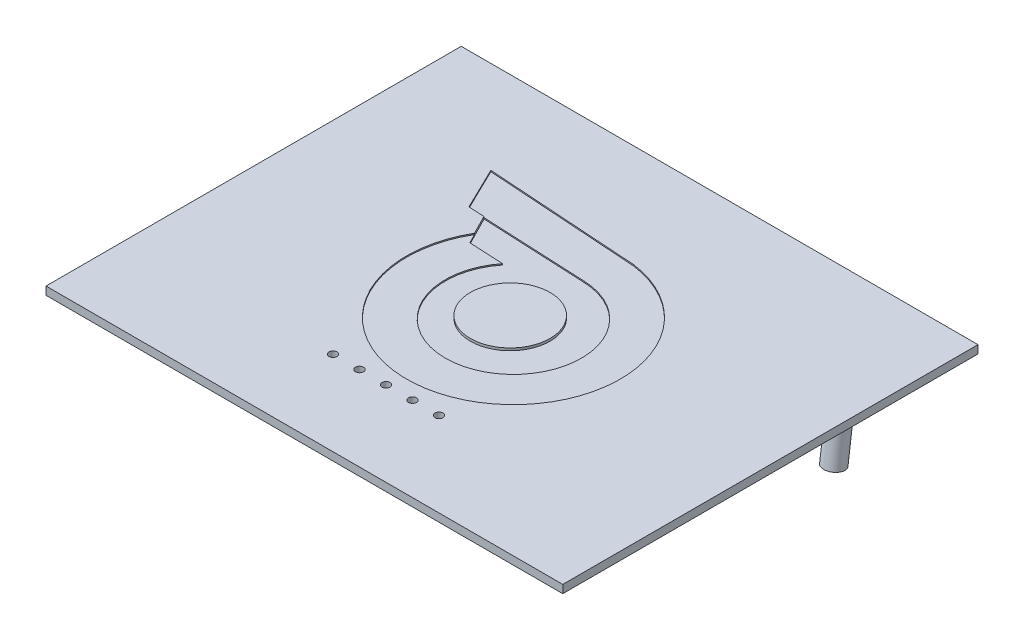
SolidWorks part; units mm, degrees
ref_plane "Front Plane" through (0, 0, 0) normal (0, 0, 1) x (1, 0, 0)
ref_plane "Top Plane" through (0, 0, 0) normal (0, 1, 0) x (1, 0, 0)
ref_plane "Right Plane" through (0, 0, 0) normal (1, 0, 0) x (0, 0, -1)
sketch "Sketch1" plane through (0, 0, 0) normal (0, 1, 0) x (1, 0, 0)
  line L1 (-64, -50.5) -> (64, -50.5)
  line L2 (-64, -50.5) -> (-64, 50.5)
  line L3 (-64, 50.5) -> (64, 50.5)
  line L4 (64, -50.5) -> (64, 50.5)
  line L5 (-64, -50.5) -> (64, 50.5) construction
  line L6 (-64, 50.5) -> (64, -50.5) construction
  point P0 (0, 0)
  dimension "D1" = 101
  dimension "D2" = 128
extrude "Boss-Extrude1" add sketch "Sketch1" along normal blind 2
sketch "Sketch2" plane through (0, 0, 0) normal (0, -1, 0) x (1, 0, 0)
  line L0 (-64, 49) -> (-62.9, 49) construction
  line L1 (-64, 50.5) -> (64, 50.5) construction
  line L2 (64, 49) -> (62.9, 49) construction
  line L3 (64, -50.5) -> (-64, -50.5) construction
  line L4 (62.9, 49) -> (61.7, 49)
  line L5 (62.9, 49) -> (62.9, -49)
  line L6 (62.9, -49) -> (61.7, -49)
  line L7 (61.7, 49) -> (61.7, -49)
  line L8 (-64, -51.87) -> (-64, 50.98) construction
  line L9 (-62.9, 49) -> (-61.7, 49)
  line L10 (-62.9, 49) -> (-62.9, -49)
  line L11 (-62.9, -49) -> (-61.7, -49)
  line L12 (-61.7, 49) -> (-61.7, -49)
  line L13 (-62.9, 49) -> (-62.9, 50.5) construction
  line L14 (64, 50.98) -> (64, -51.87) construction
  dimension "D1" = 1.1
  dimension "D2" = 1.1
  dimension "D3" = 1.2
  dimension "D4" = 1.2
  dimension "D5" = 1.5
  dimension "D6" = 1.5
  dimension "D7" = 1.5
  dimension "D8" = 1.5
extrude "Boss-Extrude2" add sketch "Sketch2" along normal blind 1
sketch "Sketch3" plane through (0, 0, 50.5) normal (0, 0, 1) x (1, 0, 0)
  line L1 (-64, 2) -> (64, 2)
  line L2 (-64, 2) -> (-64, 0)
  line L3 (-64, 0) -> (64, 0)
  line L4 (64, 2) -> (64, 0)
extrude "Boss-Extrude3" add sketch "Sketch3" along normal blind 0.48
sketch "Sketch4" plane through (0, 0, -50.5) normal (0, 0, -1) x (-1, 0, 0)
  line L1 (-64, 2) -> (64, 2)
  line L2 (-64, 2) -> (-64, 0)
  line L3 (-64, 0) -> (64, 0)
  line L4 (64, 2) -> (64, 0)
extrude "Boss-Extrude4" add sketch "Sketch4" along normal blind 1.37
sketch "Sketch5" plane through (0, -10.49, 1.3637) normal (0, 0.9917, -0.1289) x (1, 0, 0)
  circle A1 centre (-58.4589, 22.8979) radius 2.5 construction
  circle A3 centre (-58.4589, 22.8979) radius 2.5
  circle A5 centre (58.5411, 22.8979) radius 2.5 construction
  circle A7 centre (58.5411, 22.8979) radius 2.5
extrude "Boss-Extrude5" add sketch "Sketch5" along normal blind 13 from offset 2
hole_wizard "M3 Clearance Hole1" positions "Sketch7" profile "Sketch6" hole size "M3" standard "ANSI Metric"
sketch "Sketch7" plane through (0, -8.5067, 1.1059) normal (0, -0.9917, 0.1289) x (1, 0, 0)
  circle A1 centre (58.5411, -22.8979) radius 2.5 construction
  point P0 (58.5411, -22.8979)
  point P10 (58.5411, -22.8979)
  point P12 (0, 0)
sketch "Sketch6" plane through (58.5411, -11.4586, -21.6009) normal (1, 0, 0) x (0, -0.1289, -0.9917)
  line L0 (0, 0) -> (0, 11.0215)
  line L1 (0, 11.0215) -> (1.7, 10)
  line L2 (1.7, 10) -> (1.7, 0.025)
  line L3 (1.7, 0.025) -> (1.725, 0)
  line L5 (1.725, 0) -> (0, 0)
  line L6 (-1.7, 0.025) -> (-1.725, 0) construction
  line L10 (0, 11.0215) -> (-1.7, 10) construction
  line L11 (0, -6.35) -> (0, 107.95) construction
  dimension "Hole Dia." = 3.4
  dimension "Hole Depth" = 10
  dimension "Near C'Sink Dia." = 3.45
  dimension "Near C'Sink Angle" = 90
  dimension "Drill Angle" = 118
hole_wizard "M3 Clearance Hole2" positions "Sketch9" profile "Sketch8" hole size "M3" standard "ANSI Metric"
sketch "Sketch9" plane through (0, -8.5067, 1.1059) normal (0, -0.9917, 0.1289) x (1, 0, 0)
  point P0 (-58.4589, -22.9421)
  point P8 (0, 0)
sketch "Sketch8" plane through (-58.4589, -11.4643, -21.6448) normal (1, 0, 0) x (0, -0.1289, -0.9917)
  line L0 (0, 0) -> (0, 11.0215)
  line L1 (0, 11.0215) -> (1.7, 10)
  line L2 (1.7, 10) -> (1.7, 0.025)
  line L3 (1.7, 0.025) -> (1.725, 0)
  line L5 (1.725, 0) -> (0, 0)
  line L6 (-1.7, 0.025) -> (-1.725, 0) construction
  line L10 (0, 11.0215) -> (-1.7, 10) construction
  line L11 (0, -6.35) -> (0, 107.95) construction
  dimension "Hole Dia." = 3.4
  dimension "Hole Depth" = 10
  dimension "Near C'Sink Dia." = 3.45
  dimension "Near C'Sink Angle" = 90
  dimension "Drill Angle" = 118
ref_plane "Plane1" through (-19.9589, -3.8823, 45.9863) normal (1, 0, 0) x (0, 0, -1)
ref_plane "Plane2" through (18.5411, -3.8836, 45.9764) normal (0, -0.9917, 0.1289) x (-1, 0, 0)
sketch "Sketch13" plane through (0, -9.9942, 1.2992) normal (0, 0.9917, -0.1289) x (1, 0, 0)
  line L0 (-19.9589, -45.1021) -> (18.5411, -45.1021) construction
  line L1 (-19.9589, -45.1021) -> (18.5411, -45.1021)
sketch "Sketch14" plane through (0, 0, 0) normal (0, -1, 0) x (1, 0, 0)
  line L0 (-19.9589, 35.3988) -> (-19.9589, 56.5738) construction
  line L2 (18.5411, 31.0543) -> (18.5411, 29.0543) construction
  line L3 (18.5411, 29.0543) -> (-19.9589, 29.0543) construction
  line L4 (-19.9589, 31.0543) -> (-19.9589, 29.0543) construction
  line L7 (-14.2761, 31.0543) -> (-14.2761, 29.0543) construction
  line L8 (-14.2761, 29.0543) -> (-13.3954, 29.0543) construction
  line L9 (-13.3954, 31.0543) -> (-13.3954, 29.0543) construction
  line L10 (-7.7127, 31.0543) -> (-7.7127, 29.0543) construction
  line L11 (-7.7127, 29.0543) -> (-6.8319, 29.0543) construction
  line L12 (-6.8319, 31.0543) -> (-6.8319, 29.0543) construction
  line L14 (11.9777, 31.0543) -> (11.9777, 29.0543) construction
  line L15 (11.9777, 29.0543) -> (12.8584, 29.0543) construction
  line L16 (12.8584, 31.0543) -> (12.8584, 29.0543) construction
  line L18 (5.4142, 31.0543) -> (5.4142, 29.0543) construction
  line L19 (5.4142, 29.0543) -> (6.295, 29.0543) construction
  line L20 (6.295, 31.0543) -> (6.295, 29.0543) construction
  line L21 (-19.9589, 31.0543) -> (-14.2761, 31.0543) construction
  line L22 (-14.2761, 31.0543) -> (-13.3954, 31.0543) construction
  line L23 (-13.3954, 31.0543) -> (-7.7127, 31.0543) construction
  line L24 (-6.8319, 31.0543) -> (-7.7127, 31.0543) construction
  line L25 (-6.8319, 31.0543) -> (-1.1492, 31.0543) construction
  line L26 (6.295, 31.0543) -> (5.4142, 31.0543) construction
  line L27 (6.295, 31.0543) -> (11.9777, 31.0543) construction
  line L28 (11.9777, 31.0543) -> (12.8584, 31.0543) construction
  line L29 (12.8584, 31.0543) -> (18.5411, 31.0543) construction
  line L30 (-14.2761, 31.0543) -> (-13.3954, 29.0543) construction
  line L31 (-7.7127, 31.0543) -> (-6.8319, 29.0543) construction
  line L32 (5.4142, 31.0543) -> (6.295, 29.0543) construction
  line L33 (11.9777, 31.0543) -> (12.8584, 29.0543) construction
  line L34 (-19.9589, 30.0543) -> (18.5411, 30.0543) construction
  line L35 (-1.1492, 31.0543) -> (-1.1492, 29.0543) construction
  line L36 (-0.2685, 31.0543) -> (-0.2685, 29.0543) construction
  line L37 (-0.2685, 31.0543) -> (-1.1492, 31.0543) construction
  line L38 (-1.1492, 31.0543) -> (-0.2685, 29.0543) construction
  line L39 (-0.2685, 31.0543) -> (5.4142, 31.0543) construction
  circle A1 centre (-7.2723, 30.0543) radius 1
  circle A2 centre (5.8546, 30.0543) radius 1
  circle A3 centre (12.4181, 30.0543) radius 1
  circle A4 centre (-13.8358, 30.0543) radius 1
  circle A5 centre (-0.7089, 30.0543) radius 1
  point P25 (-14.2761, 31.0543)
  dimension "D1" = 2
  dimension "D2" = 38.5
sketch "Sketch15" plane through (0, 0, 0) normal (0, -1, 0) x (1, 0, 0)
  line L0 (-16.4315, 32.0543) -> (-13.8358, 30.0543) construction
  line L1 (-16.4315, 32.0543) -> (14.7611, 32.0543)
  line L3 (-16.4315, 28.0543) -> (14.7611, 28.0543)
  line L5 (14.7611, 28.0543) -> (19.7611, 28.0543)
  line L7 (14.7611, 32.0543) -> (19.7611, 32.0543)
  line L8 (19.7611, 28.0543) -> (19.7611, 32.0543)
  line L9 (-16.4315, 32.0543) -> (-21.4315, 32.0543)
  line L11 (-16.4315, 28.0543) -> (-21.4315, 28.0543)
  line L12 (-21.4315, 32.0543) -> (-21.4315, 28.0543)
  line L13 (-13.8358, 30.0543) -> (-16.4315, 28.0543) construction
  line L14 (-16.4315, 32.0543) -> (-16.4315, 28.0543) construction
  line L15 (-21.4315, 30.0543) -> (19.7611, 30.0543) construction
  circle A0 centre (12.4181, 30.0543) radius 1 construction
  circle A1 centre (5.8546, 30.0543) radius 1 construction
  circle A2 centre (-7.2723, 30.0543) radius 1 construction
  circle A3 centre (-13.8358, 30.0543) radius 1 construction
  circle A4 centre (12.4181, 30.0543) radius 1 construction
  circle A5 centre (5.8546, 30.0543) radius 1 construction
  circle A6 centre (-7.2723, 30.0543) radius 1 construction
  circle A7 centre (-13.8358, 30.0543) radius 1 construction
  point P22 (0, 0)
  dimension "D1" = 5
  dimension "D2" = 5
  dimension "D3" = 4
extrude "Cut-Extrude1" cut sketch "Sketch14" against normal blind 5
extrude "Cut-Extrude2" cut sketch "Sketch15" against normal blind 0.4
sketch "Sketch28" plane through (0, 2, 0) normal (0, 1, 0) x (1, 0, 0)
  line L0 (-105.9112, 39.4438) -> (44.0888, 39.4438) construction
  line L7 (-33.7286, 28.9336) -> (4.1341, 26.3936)
  line L8 (-33.7286, 28.9336) -> (-28.5988, 18.379)
  line L9 (-28.5988, 18.379) -> (-19.0138, 17.8876)
  line L10 (-24.7233, 18.245) -> (-21.08, 11.0937)
  line L11 (-21.08, 11.0937) -> (-12.5701, 10.6574)
  line L12 (-24.7233, 18.245) -> (1.3585, 17.016)
  circle A4 centre (0, 0) radius 9.8716
  arc A5 (-19.0138, 17.8876) -> (4.1341, 26.3936) centre (0.6344, 0.1675) ccw
  arc A6 (-12.5701, 10.6574) -> (1.3585, 17.016) centre (0.6344, 0.1675) ccw
  point P2 (0, 0)
  point P3 (0, 0)
  point P4 (0, 0)
sketch "Sketch31" plane through (0, 2, 0) normal (0, 1, 0) x (1, 0, 0)
  line L0 (-33.7286, 28.9336) -> (4.1341, 26.3936) construction
  line L1 (-33.7286, 28.9336) -> (-28.5988, 18.379) construction
  line L2 (-28.5988, 18.379) -> (-19.0138, 17.8876) construction
  line L3 (-33.7286, 28.9336) -> (4.1341, 26.3936)
  line L4 (-33.7286, 28.9336) -> (-28.5988, 18.379)
  line L5 (-28.5988, 18.379) -> (-19.0138, 17.8876)
  arc A0 (-19.0138, 17.8876) -> (4.1341, 26.3936) centre (0.6344, 0.1675) ccw construction
  arc A1 (-19.0138, 17.8876) -> (4.1341, 26.3936) centre (0.6344, 0.1675) ccw
sketch "Sketch29" plane through (0, 2, 0) normal (0, 1, 0) x (1, 0, 0)
  line L0 (-24.7233, 18.245) -> (1.3585, 17.016) construction
  line L1 (-24.7233, 18.245) -> (-21.08, 11.0937) construction
  line L2 (-21.08, 11.0937) -> (-12.5701, 10.6574) construction
  line L3 (-24.7233, 18.245) -> (1.3585, 17.016)
  line L4 (-24.7233, 18.245) -> (-21.08, 11.0937)
  line L5 (-21.08, 11.0937) -> (-12.5701, 10.6574)
  arc A0 (-12.5701, 10.6574) -> (1.3585, 17.016) centre (0.6344, 0.1675) ccw construction
  arc A1 (-12.5701, 10.6574) -> (1.3585, 17.016) centre (0.6344, 0.1675) ccw
sketch "Sketch30" plane through (0, 2, 0) normal (0, 1, 0) x (1, 0, 0)
  circle A0 centre (0, 0) radius 9.8716 construction
  circle A1 centre (0, 0) radius 9.8716
extrude "Cut-Extrude4" cut sketch "Sketch31" against normal blind 0.3
extrude "Cut-Extrude5" cut sketch "Sketch29" against normal blind 0.6
extrude "Boss-Extrude13" add sketch "Sketch30" against normal blind 0.6 from offset 0.2 separate body
